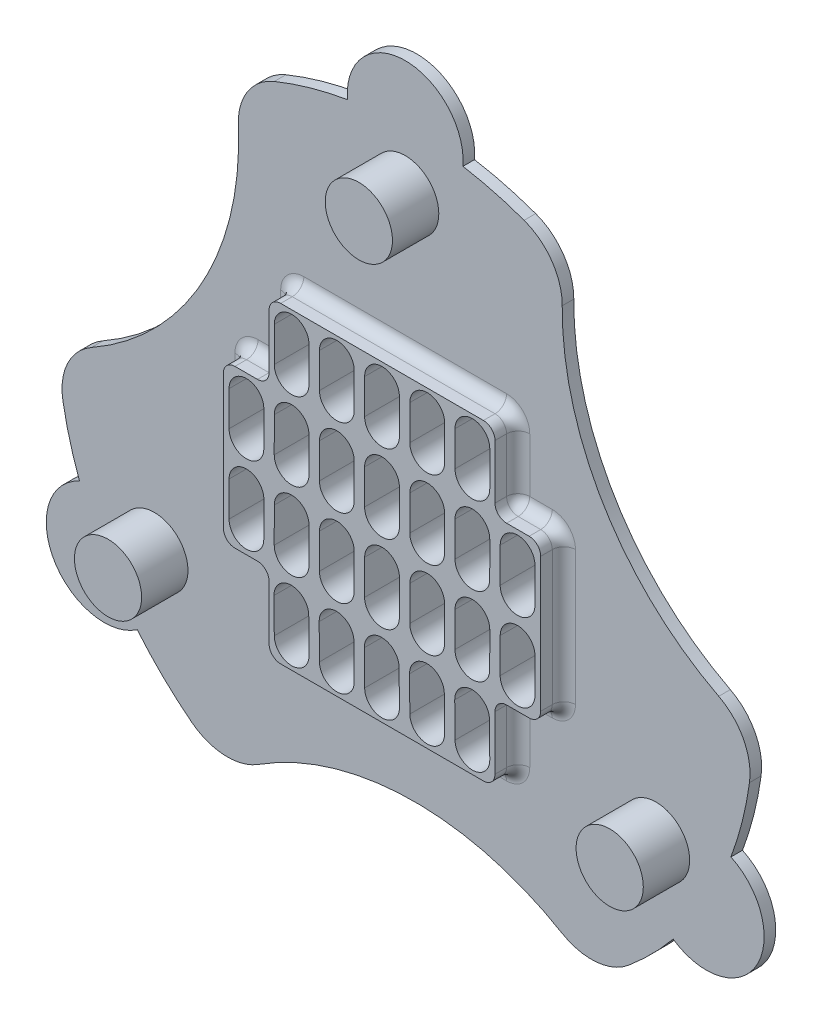
SolidWorks part; units mm, degrees
ref_plane "Спереди" through (0, 0, 0) normal (0, 0, 1) x (1, 0, 0)
ref_plane "Сверху" through (0, 0, 0) normal (0, 1, 0) x (1, 0, 0)
ref_plane "Справа" through (0, 0, 0) normal (1, 0, 0) x (0, 0, -1)
sketch "Sketch1" plane through (0, 0, 0) normal (0, 0, 1) x (1, 0, 0)
  line L0 (3.9, 6.755) -> (7.8, 0) construction
  line L2 (5.85, 10.1325) -> (11.7, 0) construction
  line L4 (7.8, 13.51) -> (15.6, 0) construction
  circle A61 centre (0, 0) radius 20
  circle A131 centre (0, 0) radius 1.25
  circle A484 centre (3.9, 0) radius 1.25
  circle A485 centre (7.8, 0) radius 1.25
  circle A486 centre (11.7, 0) radius 1.25
  circle A487 centre (15.6, 0) radius 1.25
  circle A488 centre (1.95, -3.3775) radius 1.25
  circle A489 centre (3.9, -6.755) radius 1.25
  circle A490 centre (5.85, -10.1325) radius 1.25
  circle A491 centre (7.8, -13.51) radius 1.25
  circle A492 centre (-1.95, -3.3775) radius 1.25
  circle A493 centre (-3.9, -6.755) radius 1.25
  circle A494 centre (-5.85, -10.1325) radius 1.25
  circle A495 centre (-7.8, -13.51) radius 1.25
  circle A496 centre (-3.9, 0) radius 1.25
  circle A497 centre (-7.8, 0) radius 1.25
  circle A498 centre (-11.7, 0) radius 1.25
  circle A499 centre (-15.6, 0) radius 1.25
  circle A500 centre (-1.95, 3.3775) radius 1.25
  circle A501 centre (-3.9, 6.755) radius 1.25
  circle A502 centre (-5.85, 10.1325) radius 1.25
  circle A503 centre (-7.8, 13.51) radius 1.25
  circle A504 centre (1.95, 3.3775) radius 1.25
  circle A505 centre (3.9, 6.755) radius 1.25
  circle A506 centre (5.85, 10.1325) radius 1.25
  circle A507 centre (7.8, 13.51) radius 1.25
  circle A508 centre (5.85, 3.3775) radius 1.25
  circle A509 centre (7.8, 6.755) radius 1.25
  circle A510 centre (9.75, 3.3775) radius 1.25
  circle A511 centre (11.7, 6.755) radius 1.25
  circle A512 centre (9.7491, 10.1341) radius 1.25
  circle A513 centre (13.6509, 3.3759) radius 1.25
  circle A514 centre (5.85, -3.3791) radius 1.25
  circle A515 centre (9.75, -3.3791) radius 1.25
  circle A516 centre (7.8, -6.7566) radius 1.25
  circle A517 centre (11.7, -6.7566) radius 1.25
  circle A518 centre (9.7491, -10.1356) radius 1.25
  circle A519 centre (13.6509, -3.3775) radius 1.25
  circle A520 centre (-0.0013, -6.7573) radius 1.25
  circle A521 centre (1.9487, -10.1348) radius 1.25
  circle A522 centre (-1.9513, -10.1348) radius 1.25
  circle A523 centre (-0.0013, -13.5123) radius 1.25
  circle A524 centre (-3.9032, -13.5123) radius 1.25
  circle A525 centre (3.9005, -13.5123) radius 1.25
  circle A526 centre (-5.8527, -3.3791) radius 1.25
  circle A527 centre (-7.8027, -6.7566) radius 1.25
  circle A528 centre (-9.7527, -3.3791) radius 1.25
  circle A529 centre (-11.7027, -6.7566) radius 1.25
  circle A530 centre (-13.6536, -3.3775) radius 1.25
  circle A531 centre (-9.7518, -10.1356) radius 1.25
  circle A532 centre (-5.8527, 3.3775) radius 1.25
  circle A533 centre (-9.7527, 3.3775) radius 1.25
  circle A534 centre (-7.8027, 6.755) radius 1.25
  circle A535 centre (-11.7027, 6.755) radius 1.25
  circle A536 centre (-9.7518, 10.1341) radius 1.25
  circle A537 centre (-13.6536, 3.3759) radius 1.25
  circle A538 centre (-0.0014, 6.7558) radius 1.25
  circle A539 centre (-1.9514, 10.1333) radius 1.25
  circle A540 centre (1.9486, 10.1333) radius 1.25
  circle A541 centre (-0.0014, 13.5108) radius 1.25
  circle A542 centre (3.9005, 13.5108) radius 1.25
  circle A543 centre (-3.9032, 13.5108) radius 1.25
  circle A544 centre (13.65, -1.1258) radius 2.2517 construction
  circle A545 centre (11.7009, -4.5044) radius 2.2522 construction
  circle A546 centre (9.75, -7.8834) radius 2.2522 construction
  circle A547 centre (7.7987, -11.2591) radius 2.2509 construction
  circle A548 centre (13.65, -1.1258) radius 0.65
  circle A549 centre (11.7009, -4.5044) radius 0.65
  circle A550 centre (9.75, -7.8834) radius 0.65
  circle A551 centre (7.7987, -11.2591) radius 0.65
  circle A552 centre (9.75, -1.1258) radius 0.65
  circle A553 centre (7.8009, -4.5044) radius 0.65
  circle A554 centre (5.85, -7.8834) radius 0.65
  circle A555 centre (3.8987, -11.2591) radius 0.65
  circle A556 centre (5.85, -1.1258) radius 0.65
  circle A557 centre (3.9009, -4.5044) radius 0.65
  circle A558 centre (1.95, -7.8834) radius 0.65
  circle A559 centre (-0.0013, -11.2591) radius 0.65
  circle A560 centre (1.95, -1.1258) radius 0.65
  circle A561 centre (0.0009, -4.5044) radius 0.65
  circle A562 centre (-1.95, -7.8834) radius 0.65
  circle A563 centre (-3.9013, -11.2591) radius 0.65
  circle A564 centre (-1.95, -1.1258) radius 0.65
  circle A565 centre (-3.8991, -4.5044) radius 0.65
  circle A566 centre (-5.85, -7.8834) radius 0.65
  circle A567 centre (-7.8013, -11.2591) radius 0.65
  circle A568 centre (-5.85, -1.1258) radius 0.65
  circle A569 centre (-7.7991, -4.5044) radius 0.65
  circle A570 centre (-9.75, -7.8834) radius 0.65
  circle A572 centre (-9.75, -1.1258) radius 0.65
  circle A573 centre (-11.6991, -4.5044) radius 0.65
  circle A576 centre (-13.65, -1.1258) radius 0.65
  circle A587 centre (0, 2.2517) radius 2.2517 construction
  circle A588 centre (0, 2.2517) radius 0.65
  circle A589 centre (3.9, 2.2517) radius 0.65
  circle A590 centre (7.8, 2.2517) radius 0.65
  circle A591 centre (11.7, 2.2517) radius 0.65
  circle A592 centre (15.6, 2.2517) radius 0.65
  circle A593 centre (1.9491, 5.6297) radius 2.2522 construction
  circle A594 centre (1.9491, 5.6297) radius 0.65
  circle A595 centre (5.8491, 5.6297) radius 0.65
  circle A596 centre (9.7491, 5.6297) radius 0.65
  circle A597 centre (13.6491, 5.6297) radius 0.65
  circle A598 centre (3.8991, 9.0072) radius 2.2522 construction
  circle A599 centre (3.8991, 9.0072) radius 0.65
  circle A600 centre (7.7991, 9.0072) radius 0.65
  circle A601 centre (11.6991, 9.0072) radius 0.65
  circle A602 centre (5.85, 12.3842) radius 2.2517 construction
  circle A603 centre (5.85, 12.3842) radius 0.65
  circle A604 centre (9.75, 12.3842) radius 0.65
  circle A605 centre (5.85, -14.6358) radius 0.65
  circle A606 centre (1.9509, -14.6353) radius 0.65
  circle A607 centre (-1.9491, -14.6353) radius 0.65
  circle A608 centre (-5.85, -14.6358) radius 0.65
  circle A609 centre (-15.6, 2.2517) radius 0.65
  circle A610 centre (-13.65, 5.6281) radius 0.65
  circle A611 centre (-11.7, 9.0056) radius 0.65
  circle A612 centre (-9.75, 12.3842) radius 0.65
  circle A613 centre (-5.85, 12.3842) radius 0.65
  circle A614 centre (-1.95, 12.3842) radius 0.65
  circle A615 centre (1.95, 12.3842) radius 0.65
  circle A616 centre (-7.8, 9.0056) radius 0.65
  circle A617 centre (-9.75, 5.6281) radius 0.65
  circle A618 centre (-11.7, 2.2517) radius 0.65
  circle A619 centre (-3.9, 9.0056) radius 0.65
  circle A620 centre (-5.85, 5.6281) radius 0.65
  circle A621 centre (-7.8, 2.2517) radius 0.65
  circle A622 centre (0, 9.0056) radius 0.65
  circle A623 centre (-1.95, 5.6281) radius 0.65
  circle A624 centre (-3.9, 2.2517) radius 0.65
  circle A625 centre (-15.5991, -4.5044) radius 0.65
  circle A626 centre (-13.65, -7.8834) radius 0.65
  circle A627 centre (-17.55, -7.8834) radius 0.65
  circle A628 centre (-19.5013, -11.2591) radius 0.65
  circle A629 centre (-15.6013, -11.2591) radius 0.65
  circle A630 centre (-11.7013, -11.2591) radius 0.65
  point P51 (0, 0)
  point P125 (-0.0013, -0.0008)
  point P231 (0, 0)
  dimension "D1" = 5
  dimension "D3" = 6
  dimension "D5" = 8
  dimension "D7" = 4
  dimension "D11" = 4
  dimension "D2" = 6
  dimension "D6" = 5
  dimension "D8" = 3
  dimension "D9" = 2
  dimension "D4" = 1.3
  dimension "D10" = 3
ref_plane "Plane1" through (0, 0, 10) normal (0, 0, 1) x (1, 0, 0)
sketch "Sketch2" plane through (0, 0, 10) normal (0, 0, 1) x (1, 0, 0)
  line L0 (-7.8, 13.51) -> (-7.8027, 6.755) construction
  line L1 (-9.7518, 10.1341) -> (-5.85, 10.1325) construction
  line L2 (-7.8008, 11.6325) -> (-7.8019, 8.6325) construction
  line L3 (-6.3008, 11.6319) -> (-6.3019, 8.6319)
  line L4 (-9.3008, 11.6331) -> (-9.3019, 8.6331)
  line L5 (-5.4008, 11.6331) -> (-5.4019, 8.6331)
  line L6 (-2.4008, 11.6319) -> (-2.4019, 8.6319)
  line L7 (-3.9008, 11.6325) -> (-3.9019, 8.6325) construction
  line L8 (-1.5008, 11.6331) -> (-1.5019, 8.6331)
  line L9 (1.4992, 11.6319) -> (1.4981, 8.6319)
  line L10 (-0.0008, 11.6325) -> (-0.0019, 8.6325) construction
  line L11 (2.3992, 11.6331) -> (2.3981, 8.6331)
  line L12 (5.3992, 11.6319) -> (5.3981, 8.6319)
  line L13 (3.8992, 11.6325) -> (3.8981, 8.6325) construction
  line L14 (6.2992, 11.6331) -> (6.2981, 8.6331)
  line L15 (9.2992, 11.6319) -> (9.2981, 8.6319)
  line L16 (7.7992, 11.6325) -> (7.7981, 8.6325) construction
  line L17 (-9.7518, 10.1341) -> (-9.7527, 3.3775) construction
  line L18 (-11.7027, 6.755) -> (-7.8027, 6.755) construction
  line L19 (-10.2035, 1.8767) -> (-10.202, 4.8767)
  line L22 (-9.7527, 3.3775) -> (-5.8527, 3.3775) construction
  line L25 (-7.8027, 6.755) -> (-7.8, 0) construction
  line L26 (-7.8035, 1.8775) -> (-7.8019, 4.8775) construction
  line L27 (-9.3035, 1.8782) -> (-9.3019, 4.8782)
  line L28 (-6.3035, 1.8767) -> (-6.3019, 4.8767)
  line L29 (-2.4035, 1.8767) -> (-2.4019, 4.8767)
  line L30 (-5.4035, 1.8782) -> (-5.4019, 4.8782)
  line L31 (-3.9035, 1.8775) -> (-3.9019, 4.8775) construction
  line L32 (1.4965, 1.8767) -> (1.4981, 4.8767)
  line L33 (-1.5035, 1.8782) -> (-1.5019, 4.8782)
  line L34 (-0.0035, 1.8775) -> (-0.0019, 4.8775) construction
  line L35 (5.3965, 1.8767) -> (5.3981, 4.8767)
  line L36 (2.3965, 1.8782) -> (2.3981, 4.8782)
  line L37 (3.8965, 1.8775) -> (3.8981, 4.8775) construction
  line L38 (9.2965, 1.8767) -> (9.2981, 4.8767)
  line L39 (6.2965, 1.8782) -> (6.2981, 4.8782)
  line L40 (7.7965, 1.8775) -> (7.7981, 4.8775) construction
  line L41 (13.1965, 1.8767) -> (13.1981, 4.8767)
  line L42 (10.1965, 1.8782) -> (10.1981, 4.8782)
  line L43 (11.6965, 1.8775) -> (11.6981, 4.8775) construction
  line L44 (-13.2035, 1.8782) -> (-13.2019, 4.8782)
  line L45 (-11.7035, 1.8775) -> (-11.702, 4.8775) construction
  line L46 (-9.7527, -3.3791) -> (-5.8527, -3.3791) construction
  line L47 (-7.8, 0) -> (-7.8027, -6.7566) construction
  line L48 (-7.8046, -4.8791) -> (-7.8008, -1.8791) construction
  line L49 (-9.3046, -4.8771) -> (-9.3007, -1.8771)
  line L50 (-6.3047, -4.881) -> (-6.3008, -1.881)
  line L51 (-2.4047, -4.881) -> (-2.4008, -1.881)
  line L52 (-5.4046, -4.8771) -> (-5.4007, -1.8771)
  line L53 (-3.9046, -4.8791) -> (-3.9008, -1.8791) construction
  line L54 (1.4953, -4.881) -> (1.4992, -1.881)
  line L55 (-1.5046, -4.8771) -> (-1.5007, -1.8771)
  line L56 (-0.0046, -4.8791) -> (-0.0008, -1.8791) construction
  line L57 (5.3953, -4.881) -> (5.3992, -1.881)
  line L58 (2.3954, -4.8771) -> (2.3993, -1.8771)
  line L59 (3.8954, -4.8791) -> (3.8992, -1.8791) construction
  line L60 (9.2953, -4.881) -> (9.2992, -1.881)
  line L61 (6.2954, -4.8771) -> (6.2993, -1.8771)
  line L62 (7.7954, -4.8791) -> (7.7992, -1.8791) construction
  line L63 (13.1953, -4.881) -> (13.1992, -1.881)
  line L64 (10.1954, -4.8771) -> (10.1993, -1.8771)
  line L65 (11.6954, -4.8791) -> (11.6992, -1.8791) construction
  line L66 (-10.2047, -4.881) -> (-10.2008, -1.881)
  line L67 (-13.2046, -4.8771) -> (-13.2007, -1.8771)
  line L68 (-11.7046, -4.8791) -> (-11.7008, -1.8791) construction
  line L69 (-9.7518, -10.1356) -> (-5.482, -10.1356) construction
  line L70 (-7.8027, -6.7566) -> (-7.8, -13.51) construction
  line L71 (-7.8259, -8.6356) -> (-7.8007, -11.6356) construction
  line L72 (-6.3259, -8.623) -> (-6.3008, -11.623)
  line L73 (-9.3258, -8.6482) -> (-9.3007, -11.6482)
  line L74 (-5.4258, -8.6482) -> (-5.4007, -11.6482)
  line L75 (-2.4259, -8.623) -> (-2.4008, -11.623)
  line L76 (-3.9259, -8.6356) -> (-3.9007, -11.6356) construction
  line L77 (-1.5258, -8.6482) -> (-1.5007, -11.6482)
  line L78 (1.4741, -8.623) -> (1.4992, -11.623)
  line L79 (-0.0259, -8.6356) -> (-0.0007, -11.6356) construction
  line L80 (2.3742, -8.6482) -> (2.3993, -11.6482)
  line L81 (5.3741, -8.623) -> (5.3992, -11.623)
  line L82 (3.8741, -8.6356) -> (3.8993, -11.6356) construction
  line L83 (6.2742, -8.6482) -> (6.2993, -11.6482)
  line L84 (9.2741, -8.623) -> (9.2992, -11.623)
  line L85 (7.7741, -8.6356) -> (7.7993, -11.6356) construction
  arc A0 (-6.3008, 11.6319) -> (-9.3008, 11.6331) centre (-7.8008, 11.6325) ccw
  arc A1 (-9.3019, 8.6331) -> (-6.3019, 8.6319) centre (-7.8019, 8.6325) ccw
  arc A2 (-2.4008, 11.6319) -> (-5.4008, 11.6331) centre (-3.9008, 11.6325) ccw
  arc A3 (-5.4019, 8.6331) -> (-2.4019, 8.6319) centre (-3.9019, 8.6325) ccw
  arc A4 (1.4992, 11.6319) -> (-1.5008, 11.6331) centre (-0.0008, 11.6325) ccw
  arc A5 (-1.5019, 8.6331) -> (1.4981, 8.6319) centre (-0.0019, 8.6325) ccw
  arc A6 (5.3992, 11.6319) -> (2.3992, 11.6331) centre (3.8992, 11.6325) ccw
  arc A7 (2.3981, 8.6331) -> (5.3981, 8.6319) centre (3.8981, 8.6325) ccw
  arc A8 (9.2992, 11.6319) -> (6.2992, 11.6331) centre (7.7992, 11.6325) ccw
  arc A9 (6.2981, 8.6331) -> (9.2981, 8.6319) centre (7.7981, 8.6325) ccw
  arc A14 (-9.3035, 1.8782) -> (-6.3035, 1.8767) centre (-7.8035, 1.8775) ccw
  arc A15 (-6.3019, 4.8767) -> (-9.3019, 4.8782) centre (-7.8019, 4.8775) ccw
  arc A16 (-5.4035, 1.8782) -> (-2.4035, 1.8767) centre (-3.9035, 1.8775) ccw
  arc A17 (-2.4019, 4.8767) -> (-5.4019, 4.8782) centre (-3.9019, 4.8775) ccw
  arc A18 (-1.5035, 1.8782) -> (1.4965, 1.8767) centre (-0.0035, 1.8775) ccw
  arc A19 (1.4981, 4.8767) -> (-1.5019, 4.8782) centre (-0.0019, 4.8775) ccw
  arc A20 (2.3965, 1.8782) -> (5.3965, 1.8767) centre (3.8965, 1.8775) ccw
  arc A21 (5.3981, 4.8767) -> (2.3981, 4.8782) centre (3.8981, 4.8775) ccw
  arc A22 (6.2965, 1.8782) -> (9.2965, 1.8767) centre (7.7965, 1.8775) ccw
  arc A23 (9.2981, 4.8767) -> (6.2981, 4.8782) centre (7.7981, 4.8775) ccw
  arc A24 (10.1965, 1.8782) -> (13.1965, 1.8767) centre (11.6965, 1.8775) ccw
  arc A25 (13.1981, 4.8767) -> (10.1981, 4.8782) centre (11.6981, 4.8775) ccw
  arc A26 (-13.2035, 1.8782) -> (-10.2035, 1.8767) centre (-11.7035, 1.8775) ccw
  arc A27 (-10.202, 4.8767) -> (-13.2019, 4.8782) centre (-11.702, 4.8775) ccw
  arc A28 (-9.3046, -4.8771) -> (-6.3047, -4.881) centre (-7.8046, -4.8791) ccw
  arc A29 (-6.3008, -1.881) -> (-9.3007, -1.8771) centre (-7.8008, -1.8791) ccw
  arc A30 (-5.4046, -4.8771) -> (-2.4047, -4.881) centre (-3.9046, -4.8791) ccw
  arc A31 (-2.4008, -1.881) -> (-5.4007, -1.8771) centre (-3.9008, -1.8791) ccw
  arc A32 (-1.5046, -4.8771) -> (1.4953, -4.881) centre (-0.0046, -4.8791) ccw
  arc A33 (1.4992, -1.881) -> (-1.5007, -1.8771) centre (-0.0008, -1.8791) ccw
  arc A34 (2.3954, -4.8771) -> (5.3953, -4.881) centre (3.8954, -4.8791) ccw
  arc A35 (5.3992, -1.881) -> (2.3993, -1.8771) centre (3.8992, -1.8791) ccw
  arc A36 (6.2954, -4.8771) -> (9.2953, -4.881) centre (7.7954, -4.8791) ccw
  arc A37 (9.2992, -1.881) -> (6.2993, -1.8771) centre (7.7992, -1.8791) ccw
  arc A38 (10.1954, -4.8771) -> (13.1953, -4.881) centre (11.6954, -4.8791) ccw
  arc A39 (13.1992, -1.881) -> (10.1993, -1.8771) centre (11.6992, -1.8791) ccw
  arc A40 (-13.2046, -4.8771) -> (-10.2047, -4.881) centre (-11.7046, -4.8791) ccw
  arc A41 (-10.2008, -1.881) -> (-13.2007, -1.8771) centre (-11.7008, -1.8791) ccw
  arc A42 (-6.3259, -8.623) -> (-9.3258, -8.6482) centre (-7.8259, -8.6356) ccw
  arc A43 (-9.3007, -11.6482) -> (-6.3008, -11.623) centre (-7.8007, -11.6356) ccw
  arc A44 (-2.4259, -8.623) -> (-5.4258, -8.6482) centre (-3.9259, -8.6356) ccw
  arc A45 (-5.4007, -11.6482) -> (-2.4008, -11.623) centre (-3.9007, -11.6356) ccw
  arc A46 (1.4741, -8.623) -> (-1.5258, -8.6482) centre (-0.0259, -8.6356) ccw
  arc A47 (-1.5007, -11.6482) -> (1.4992, -11.623) centre (-0.0007, -11.6356) ccw
  arc A48 (5.3741, -8.623) -> (2.3742, -8.6482) centre (3.8741, -8.6356) ccw
  arc A49 (2.3993, -11.6482) -> (5.3992, -11.623) centre (3.8993, -11.6356) ccw
  arc A50 (9.2741, -8.623) -> (6.2742, -8.6482) centre (7.7741, -8.6356) ccw
  arc A51 (6.2993, -11.6482) -> (9.2992, -11.623) centre (7.7993, -11.6356) ccw
  circle A52 centre (0, 0) radius 16.85 construction
  circle A53 centre (0, 0) radius 18.85
  point P10 (-7.8014, 10.1325)
  point P18 (-3.9014, 10.1325)
  point P25 (-0.0014, 10.1325)
  point P32 (3.8986, 10.1325)
  point P39 (7.7986, 10.1325)
  point P50 (-11.7027, 3.3775)
  point P58 (-7.8027, 3.3775)
  point P68 (-3.9027, 3.3775)
  point P75 (-0.0027, 3.3775)
  point P82 (3.8973, 3.3775)
  point P89 (7.7973, 3.3775)
  point P96 (11.6973, 3.3775)
  point P108 (-7.8027, -3.3791)
  point P116 (-3.9027, -3.3791)
  point P123 (-0.0027, -3.3791)
  point P130 (3.8973, -3.3791)
  point P137 (7.7973, -3.3791)
  point P144 (11.6973, -3.3791)
  point P151 (-11.7027, -3.3791)
  point P162 (-7.8133, -10.1356)
  point P170 (-3.9133, -10.1356)
  point P177 (-0.0133, -10.1356)
  point P184 (3.8867, -10.1356)
  point P191 (7.7867, -10.1356)
  dimension "D1" = 3
  dimension "D15" = 2
  dimension "D2" = 3
  dimension "D4" = 2
  dimension "D5" = 3
  dimension "D6" = 3
  dimension "D7" = 3
  dimension "D9" = 3
  dimension "D12" = 3
  dimension "D13" = 3
  dimension "D3" = 5
  dimension "D8" = 6
  dimension "D10" = 6
  dimension "D11" = 2
  dimension "D14" = 5
extrude "Boss-Extrude1" add sketch "Sketch2" along normal blind 1
sketch "Sketch3" plane through (0, 0, 11) normal (0, 0, 1) x (1, 0, 0)
  circle A0 centre (0, 0) radius 17.6
  circle A1 centre (0, 0) radius 30
extrude "Boss-Extrude2" add sketch "Sketch3" against normal blind 1
sketch "Sketch4" plane through (0, 0, 11) normal (0, 0, 1) x (1, 0, 0)
  circle A0 centre (0, 0) radius 25 construction
  circle A1 centre (0, 25) radius 2.9
  circle A2 centre (21.6506, -12.5) radius 2.9
  circle A3 centre (-21.6506, -12.5) radius 2.9
  point P11 (0, 0)
  dimension "D1" = 3
extrude "Boss-Extrude3" add sketch "Sketch4" along normal blind 4
sketch "Sketch6" plane through (0, 0, 10) normal (0, 0, -1) x (-1, 0, 0)
  circle A0 centre (0, 30) radius 5
  circle A1 centre (0, 0) radius 30 construction
  circle A2 centre (25.9808, -15) radius 5
  circle A3 centre (-25.9808, -15) radius 5
  point P10 (0, 0)
  dimension "D1" = 3
extrude "Boss-Extrude4" add sketch "Sketch6" against normal blind 1
sketch "Sketch5" plane through (0, 0, 10) normal (0, 0, -1) x (-1, 0, 0)
  circle A0 centre (0, 25) radius 3
  circle A1 centre (21.6506, -12.5) radius 3
  circle A2 centre (-21.6506, -12.5) radius 3
sketch "Sketch7" plane through (0, 0, 10) normal (0, 0, -1) x (-1, 0, 0)
  line L0 (0, 0) -> (-38.5501, 23.214) construction
  circle A0 centre (0, 0) radius 45 construction
  circle A1 centre (-38.5501, 23.214) radius 25
  circle A2 centre (39.379, 21.7783) radius 25
  circle A3 centre (-0.8289, -44.9924) radius 25
  circle A4 centre (0, 0) radius 19 construction
  point P11 (0, 0)
  dimension "D1" = 3
extrude "Cut-Extrude2" cut sketch "Sketch7" against normal blind 1
fillet "Fillet1" radius 5 6 edges at (-14.7586, 26.1186, 10.5) (-29.9681, -1.3827, 10.5) (-15.2401, -25.8407, 10.5) (16.1815, -25.2618, 10.5) (29.9987, -0.278, 10.5) (13.7866, 26.6445, 10.5)
extrude "Boss-Extrude5" add sketch "Sketch2<2>" along normal blind 3
sketch "Sketch2<2>" plane through (0, 0, 10) normal (0, 0, 1) x (1, 0, 0) same geometry as "Sketch2"
sketch "Sketch8" plane through (0, 0, 13) normal (0, 0, 1) x (1, 0, 0)
  line L0 (0, 0) -> (6.0128, 0) construction
  line L1 (-9.7495, -6.7926) -> (9.7495, -6.7926)
  line L2 (0, 0) -> (0, 5.1095) construction
  line L3 (-9.7495, 13.4736) -> (9.7495, 13.4736)
  line L4 (-9.7495, 13.4736) -> (-9.7495, 6.7926)
  line L5 (-9.7495, 6.7926) -> (9.7495, 6.7926)
  line L6 (9.7495, 13.4736) -> (9.7495, 6.7926)
  line L7 (-9.7495, 13.4736) -> (9.7495, 6.7926) construction
  line L8 (-9.7495, 6.7926) -> (9.7495, 13.4736) construction
  line L9 (-13.6953, -6.7926) -> (13.6953, -6.7926)
  line L10 (-13.6953, -6.7926) -> (-13.6953, 6.7926)
  line L11 (-13.6953, 6.7926) -> (13.6953, 6.7926)
  line L12 (13.6953, -6.7926) -> (13.6953, 6.7926)
  line L13 (-13.6953, -6.7926) -> (13.6953, 6.7926) construction
  line L14 (-13.6953, 6.7926) -> (13.6953, -6.7926) construction
  line L15 (9.7495, -13.4736) -> (9.7495, -6.7926)
  line L16 (-9.7495, -13.4736) -> (9.7495, -13.4736)
  line L17 (-9.7495, -13.4736) -> (-9.7495, -6.7926)
  circle A0 centre (0, 0) radius 20.5111
  point P3 (0, 10.1331)
extrude "Cut-Extrude3" cut sketch "Sketch8" against normal blind 2 contours A0 L16 L17 L9 L10 L11 L4 L3 L6 L12 L15 region at (-19.9309, 0, 13)
fillet "Fillet2" radius 1 12 edges at (9.7495, 13.4736, 12) (9.7495, 6.7926, 12) (13.6953, 6.7926, 12) (13.6953, -6.7926, 12) (9.7495, -6.7926, 12) (9.7495, -13.4736, 12) (-9.7495, -13.4736, 12) (-9.7495, -6.7926, 12) (-13.6953, -6.7926, 12) (-13.6953, 6.7926, 12) (-9.7495, 6.7926, 12) (-9.7495, 13.4736, 12)
fillet "Fillet3" radius 1 24 edges at (-9.4566, 13.1807, 11) (0, 13.4736, 11) (9.4566, 13.1807, 11) (9.7495, 10.1331, 11) (10.0424, 7.0855, 11) (11.7224, 6.7926, 11) (13.4024, 6.4997, 11) (13.6953, 0, 11) (13.4024, -6.4997, 11) (11.7224, -6.7926, 11) (10.0424, -7.0855, 11) (9.7495, -10.1331, 11) (9.4566, -13.1807, 11) (0, -13.4736, 11) (-9.4566, -13.1807, 11) (-9.7495, -10.1331, 11) (-10.0424, -7.0855, 11) (-11.7224, -6.7926, 11) (-13.4024, -6.4997, 11) (-13.6953, 0, 11) (-13.4024, 6.4997, 11) (-11.7224, 6.7926, 11) (-10.0424, 7.0855, 11) (-9.7495, 10.1331, 11)
